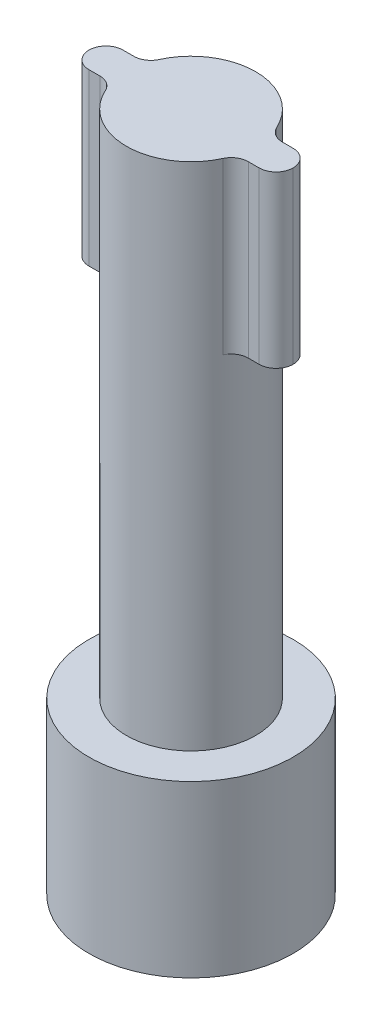
SolidWorks part; units mm, degrees
ref_plane "Ebene vorne" through (0, 0, 0) normal (0, 0, 1) x (1, 0, 0)
ref_plane "Ebene oben" through (0, 0, 0) normal (0, 1, 0) x (1, 0, 0)
ref_plane "Ebene rechts" through (0, 0, 0) normal (1, 0, 0) x (0, 0, -1)
sketch "Skizze2" plane through (0, 0, 0) normal (0, 1, 0) x (1, 0, 0)
  circle A0 centre (0, 0) radius 0.95
  dimension "D1" = 1.9
extrude "Aufsatz-Linear austragen1" add sketch "Skizze2" along normal blind 10
sketch "Skizze3" plane through (0, 10, 0) normal (0, 1, 0) x (1, 0, 0)
  line L1 (-1.5, -0.25) -> (1.5, -0.25)
  line L2 (-1.5, -0.25) -> (-1.5, 0.25)
  line L3 (-1.5, 0.25) -> (1.5, 0.25)
  line L4 (1.5, -0.25) -> (1.5, 0.25)
  line L5 (-1.5, -0.25) -> (1.5, 0.25) construction
  line L6 (-1.5, 0.25) -> (1.5, -0.25) construction
  point P0 (0, 0)
  dimension "D1" = 3
  dimension "D2" = 0.5
extrude "Aufsatz-Linear austragen2" add sketch "Skizze3" against normal blind 2.5
fillet "Verrundung2" radius 0.25 8 edges at (0.9165, 8.75, 0.25) (1.5, 8.75, 0.25) (1.5, 8.75, -0.25) (0.9165, 8.75, -0.25) (-0.9165, 8.75, -0.25) (-1.5, 8.75, -0.25) (-1.5, 8.75, 0.25) (-0.9165, 8.75, 0.25)
ref_axis "Achse1" through (0, 10, 0) along (0, -1, 0)
sketch "Skizze5" plane through (0, 0, 0) normal (0, -1, 0) x (1, 0, 0)
  circle A0 centre (0, 0) radius 1.5
extrude "Aufsatz-Linear austragen3" add sketch "Skizze5" against normal blind 2.5
